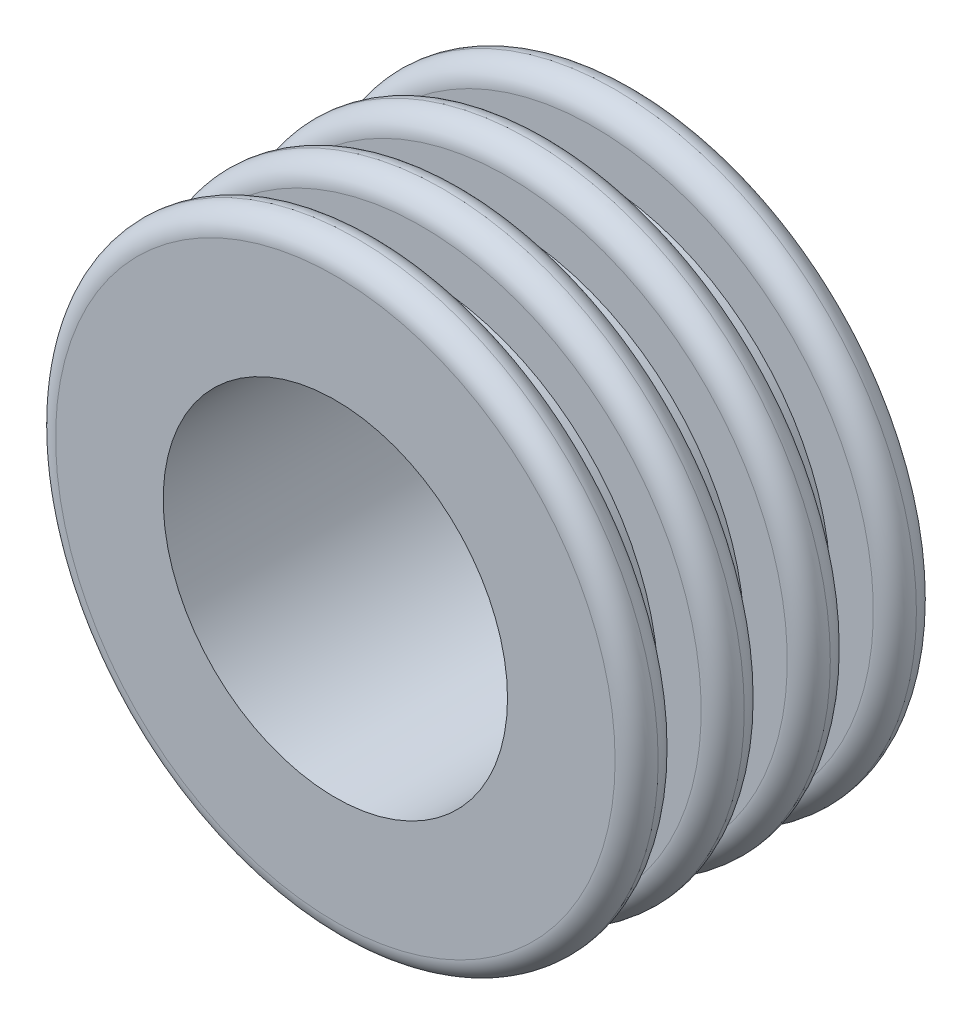
SolidWorks part; units mm, degrees
material "6061 合金"
ref_plane "前视基准面" through (0, 0, 0) normal (0, 0, 1) x (1, 0, 0)
ref_plane "上视基准面" through (0, 0, 0) normal (0, 1, 0) x (1, 0, 0)
ref_plane "右视基准面" through (0, 0, 0) normal (1, 0, 0) x (0, 0, -1)
sketch "草图1" plane through (0, 0, 0) normal (0, 0, 1) x (1, 0, 0)
  circle A0 centre (0, 0) radius 4
  circle A1 centre (0, 0) radius 7
  dimension "D1" = 8
  dimension "D2" = 14
extrude "凸台-拉伸1" add sketch "草图1" along normal blind 7
sketch "草图2" plane through (0, 0, 0) normal (1, 0, 0) x (0, 0, -1)
  line L0 (0, 0) -> (-7, 0) construction
  line L1 (-3.5, 0) -> (-3.5, 9.5205) construction
  line L2 (-7, 7) -> (-7, -7) construction
  line L3 (-6, 7) -> (-5, 7)
  line L4 (-6, 7) -> (-6, 5.5)
  line L5 (-6, 5.5) -> (-5, 5.5)
  line L6 (-5, 7) -> (-5, 5.5)
  line L7 (-2, 7) -> (-2, 5.5)
  line L8 (-1, 5.5) -> (-2, 5.5)
  line L9 (-1, 7) -> (-1, 5.5)
  line L10 (-1, 7) -> (-2, 7)
  line L13 (-4, 7) -> (-3, 7)
  line L14 (-4, 7) -> (-4, 5.5)
  line L15 (-4, 5.5) -> (-3, 5.5)
  line L16 (-3, 7) -> (-3, 5.5)
  dimension "D1" = 1
  dimension "D2" = 1
  dimension "D3" = 1.5
  dimension "D4" = 1
  dimension "D5" = 1
  dimension "D6" = 5.5
revolve "切除-旋转1" cut sketch "草图2" angle 360 about L0
fillet "圆角1" radius 0.5 8 edges at (-7, 0, 4) (-7, 0, 3) (-7, 0, 1) (-7, 0, 2) (-7, 0, 6) (-7, 0, 5) (7, 0, 0) (7, 0, 7)
